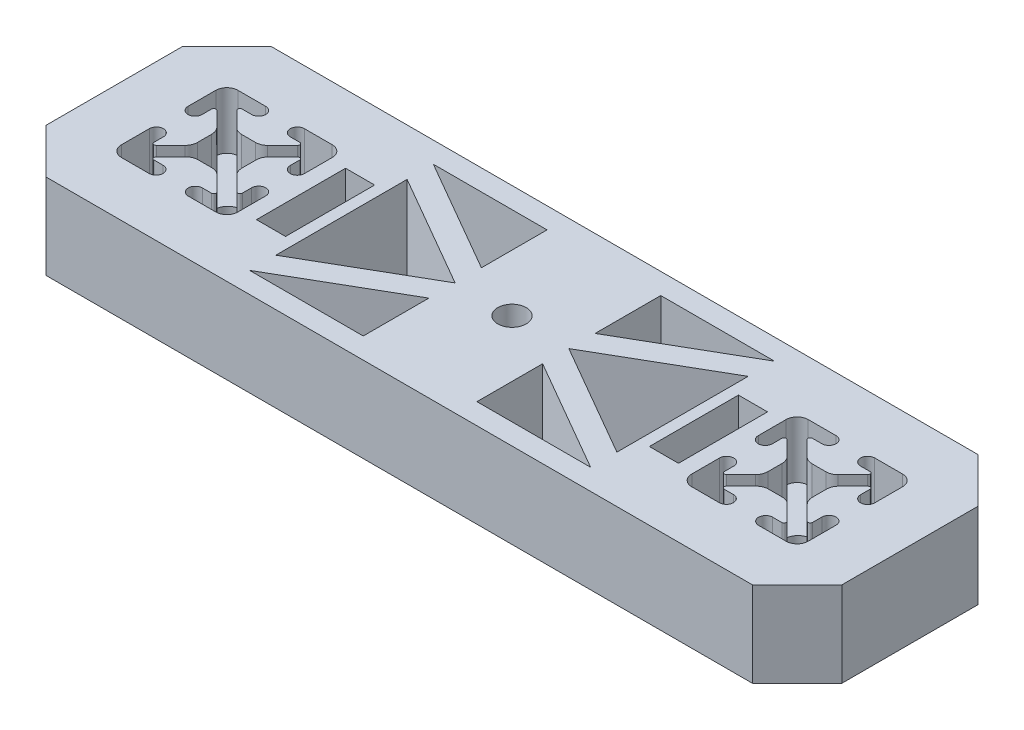
SolidWorks part; units mm, degrees
ref_plane "Front" through (0, 0, 0) normal (0, 0, 1) x (1, 0, 0)
ref_plane "Top" through (0, 0, 0) normal (0, 1, 0) x (1, 0, 0)
ref_plane "Right" through (0, 0, 0) normal (1, 0, 0) x (0, 0, -1)
sketch "Sketch1" plane through (0, 0, 0) normal (0, 1, 0) x (1, 0, 0)
  line L1 (0, 0) -> (177.8, 0)
  line L2 (0, 0) -> (0, 50.4)
  line L3 (0, 50.4) -> (177.8, 50.4)
  line L4 (177.8, 0) -> (177.8, 50.4)
  dimension "D1" = 177.8
  dimension "D2" = 50.4
extrude "Boss-Extrude1" add sketch "Sketch1" along normal blind 6.35
sketch "Sketch2" plane through (0, 6.35, 0) normal (0, 1, 0) x (1, 0, 0)
  line L0 (37.6996, 29.52) -> (37.6996, 35.7372) construction
  line L1 (35.7368, 37.7) -> (29.5196, 37.7) construction
  line L2 (29.5196, 35.56) -> (31.619, 35.56) construction
  line L3 (32.3326, 33.8353) -> (28.9966, 30.504) construction
  line L4 (26.7566, 29.5771) -> (23.643, 29.5771) construction
  line L5 (21.403, 30.504) -> (18.067, 33.8353) construction
  line L6 (18.7806, 35.56) -> (20.88, 35.56) construction
  line L7 (20.88, 37.7) -> (14.6628, 37.7) construction
  line L8 (12.7, 35.7372) -> (12.7, 29.52) construction
  line L9 (14.84, 29.52) -> (14.84, 31.5965) construction
  line L10 (16.5637, 32.3112) -> (19.7659, 29.1135) construction
  line L11 (20.743, 26.7568) -> (20.743, 23.6432) construction
  line L12 (19.7659, 21.2865) -> (16.5637, 18.0888) construction
  line L13 (14.84, 18.8035) -> (14.84, 20.88) construction
  line L14 (12.7, 20.88) -> (12.7, 14.6628) construction
  line L15 (14.6628, 12.7) -> (20.8121, 12.7) construction
  line L16 (20.8121, 14.84) -> (18.7806, 14.84) construction
  line L17 (18.067, 16.5647) -> (21.403, 19.896) construction
  line L18 (23.643, 20.8229) -> (26.7566, 20.8229) construction
  line L19 (28.9966, 19.896) -> (32.3326, 16.5647) construction
  line L20 (31.619, 14.84) -> (29.5875, 14.84) construction
  line L21 (29.5875, 12.7) -> (35.7368, 12.7) construction
  line L22 (37.6996, 14.6628) -> (37.6996, 20.88) construction
  line L23 (35.5596, 20.88) -> (35.5596, 18.8035) construction
  line L24 (33.8359, 18.0888) -> (30.6337, 21.2865) construction
  line L25 (29.6566, 23.6432) -> (29.6566, 26.7568) construction
  line L26 (30.6337, 29.1135) -> (33.8359, 32.3112) construction
  line L27 (35.5596, 31.5965) -> (35.5596, 29.52) construction
  line L28 (0, 50.4) -> (0, 0) construction
  line L29 (177.8, 50.4) -> (0, 50.4) construction
  line L30 (0, 0) -> (177.8, 0) construction
  line L31 (88.9, 50.4) -> (88.9, 0) construction
  line L32 (142.2404, 31.5965) -> (142.2404, 29.52) construction
  line L33 (147.1663, 29.1135) -> (143.9641, 32.3112) construction
  line L34 (148.1434, 23.6432) -> (148.1434, 26.7568) construction
  line L35 (143.9641, 18.0888) -> (147.1663, 21.2865) construction
  line L36 (142.2404, 20.88) -> (142.2404, 18.8035) construction
  line L37 (140.1004, 14.6628) -> (140.1004, 20.88) construction
  line L38 (148.2125, 12.7) -> (142.0632, 12.7) construction
  line L39 (146.181, 14.84) -> (148.2125, 14.84) construction
  line L40 (148.8034, 19.896) -> (145.4674, 16.5647) construction
  line L41 (154.157, 20.8229) -> (151.0434, 20.8229) construction
  line L42 (159.733, 16.5647) -> (156.397, 19.896) construction
  line L43 (156.9879, 14.84) -> (159.0194, 14.84) construction
  line L44 (163.1372, 12.7) -> (156.9879, 12.7) construction
  line L45 (165.1, 20.88) -> (165.1, 14.6628) construction
  line L46 (162.96, 18.8035) -> (162.96, 20.88) construction
  line L47 (158.0341, 21.2865) -> (161.2363, 18.0888) construction
  line L48 (157.057, 26.7568) -> (157.057, 23.6432) construction
  line L49 (161.2363, 32.3112) -> (158.0341, 29.1135) construction
  line L50 (162.96, 29.52) -> (162.96, 31.5965) construction
  line L51 (165.1, 35.7372) -> (165.1, 29.52) construction
  line L52 (156.92, 37.7) -> (163.1372, 37.7) construction
  line L53 (159.0194, 35.56) -> (156.92, 35.56) construction
  line L54 (156.397, 30.504) -> (159.733, 33.8353) construction
  line L55 (151.0434, 29.5771) -> (154.157, 29.5771) construction
  line L56 (145.4674, 33.8353) -> (148.8034, 30.504) construction
  line L57 (148.2804, 35.56) -> (146.181, 35.56) construction
  line L58 (142.0632, 37.7) -> (148.2804, 37.7) construction
  line L59 (140.1004, 29.52) -> (140.1004, 35.7372) construction
  line L60 (38.2076, 29.52) -> (38.2076, 35.7372)
  line L62 (0, 50.4) -> (0, 0)
  line L63 (0, 0) -> (177.8, 0)
  line L64 (177.8, 50.4) -> (177.8, 0)
  line L65 (35.7368, 38.208) -> (29.5196, 38.208)
  line L66 (29.5196, 35.052) -> (31.619, 35.052)
  line L67 (31.9737, 34.1948) -> (28.6376, 30.8635)
  line L68 (26.7566, 30.0851) -> (23.643, 30.0851)
  line L69 (21.762, 30.8635) -> (18.4259, 34.1948)
  line L70 (18.7806, 35.052) -> (20.88, 35.052)
  line L71 (20.88, 38.208) -> (14.6628, 38.208)
  line L72 (12.192, 35.7372) -> (12.192, 29.52)
  line L73 (15.348, 29.52) -> (15.348, 31.5965)
  line L74 (16.2047, 31.9517) -> (19.4069, 28.7541)
  line L75 (20.235, 26.7568) -> (20.235, 23.6432)
  line L76 (19.4069, 21.6459) -> (16.2047, 18.4483)
  line L77 (15.348, 18.8035) -> (15.348, 20.88)
  line L78 (12.192, 20.88) -> (12.192, 14.6628)
  line L79 (14.6628, 12.192) -> (20.8121, 12.192)
  line L80 (20.8121, 15.348) -> (18.7806, 15.348)
  line L81 (18.4259, 16.2052) -> (21.762, 19.5365)
  line L82 (23.643, 20.3149) -> (26.7566, 20.3149)
  line L83 (28.6376, 19.5365) -> (31.9737, 16.2052)
  line L84 (31.619, 15.348) -> (29.5875, 15.348)
  line L85 (29.5875, 12.192) -> (35.7368, 12.192)
  line L86 (38.2076, 14.6628) -> (38.2076, 20.88)
  line L87 (35.0516, 20.88) -> (35.0516, 18.8035)
  line L88 (34.1949, 18.4483) -> (30.9927, 21.6459)
  line L89 (30.1646, 23.6432) -> (30.1646, 26.7568)
  line L90 (30.9927, 28.7541) -> (34.1949, 31.9517)
  line L91 (35.0516, 31.5965) -> (35.0516, 29.52)
  line L92 (142.7484, 31.5965) -> (142.7484, 29.52)
  line L93 (139.5924, 29.52) -> (139.5924, 35.7372)
  line L94 (142.0632, 38.208) -> (148.2804, 38.208)
  line L95 (148.2804, 35.052) -> (146.181, 35.052)
  line L96 (145.8263, 34.1948) -> (149.1624, 30.8635)
  line L97 (151.0434, 30.0851) -> (154.157, 30.0851)
  line L98 (156.038, 30.8635) -> (159.3741, 34.1948)
  line L99 (159.0194, 35.052) -> (156.92, 35.052)
  line L100 (156.92, 38.208) -> (163.1372, 38.208)
  line L101 (165.608, 35.7372) -> (165.608, 29.52)
  line L102 (162.452, 29.52) -> (162.452, 31.5965)
  line L103 (161.5953, 31.9517) -> (158.3931, 28.7541)
  line L104 (157.565, 26.7568) -> (157.565, 23.6432)
  line L105 (158.3931, 21.6459) -> (161.5953, 18.4483)
  line L106 (162.452, 18.8035) -> (162.452, 20.88)
  line L107 (165.608, 20.88) -> (165.608, 14.6628)
  line L108 (163.1372, 12.192) -> (156.9879, 12.192)
  line L109 (156.9879, 15.348) -> (159.0194, 15.348)
  line L110 (159.3741, 16.2052) -> (156.038, 19.5365)
  line L111 (154.157, 20.3149) -> (151.0434, 20.3149)
  line L112 (149.1624, 19.5365) -> (145.8263, 16.2052)
  line L113 (146.181, 15.348) -> (148.2125, 15.348)
  line L114 (148.2125, 12.192) -> (142.0632, 12.192)
  line L115 (139.5924, 14.6628) -> (139.5924, 20.88)
  line L116 (142.7484, 20.88) -> (142.7484, 18.8035)
  line L117 (143.6051, 18.4483) -> (146.8073, 21.6459)
  line L118 (147.6354, 23.6432) -> (147.6354, 26.7568)
  line L119 (146.8073, 28.7541) -> (143.6051, 31.9517)
  line L120 (177.8, 50.4) -> (0, 50.4)
  arc A1 (37.6996, 35.7372) -> (35.7368, 37.7) centre (35.7368, 35.7372) ccw construction
  arc A2 (29.5196, 37.7) -> (29.5196, 35.56) centre (29.5196, 36.63) ccw construction
  arc A3 (31.619, 35.56) -> (32.3326, 33.8353) centre (31.619, 34.55) cw construction
  arc A4 (28.9966, 30.504) -> (26.7566, 29.5771) centre (26.7566, 32.7471) cw construction
  arc A5 (23.643, 29.5771) -> (21.403, 30.504) centre (23.643, 32.7471) cw construction
  arc A6 (18.067, 33.8353) -> (18.7806, 35.56) centre (18.7806, 34.55) cw construction
  arc A7 (20.88, 35.56) -> (20.88, 37.7) centre (20.88, 36.63) ccw construction
  arc A8 (14.6628, 37.7) -> (12.7, 35.7372) centre (14.6628, 35.7372) ccw construction
  arc A9 (12.7, 29.52) -> (14.84, 29.52) centre (13.77, 29.52) ccw construction
  arc A10 (14.84, 31.5965) -> (16.5637, 32.3112) centre (15.85, 31.5965) cw construction
  arc A11 (19.7659, 29.1135) -> (20.743, 26.7568) centre (17.4126, 26.7568) cw construction
  arc A12 (20.743, 23.6432) -> (19.7659, 21.2865) centre (17.4126, 23.6432) cw construction
  arc A13 (16.5637, 18.0888) -> (14.84, 18.8035) centre (15.85, 18.8035) cw construction
  arc A14 (14.84, 20.88) -> (12.7, 20.88) centre (13.77, 20.88) ccw construction
  arc A15 (12.7, 14.6628) -> (14.6628, 12.7) centre (14.6628, 14.6628) ccw construction
  arc A16 (20.8121, 12.7) -> (20.8121, 14.84) centre (20.8121, 13.77) ccw construction
  arc A17 (18.7806, 14.84) -> (18.067, 16.5647) centre (18.7806, 15.85) cw construction
  arc A18 (21.403, 19.896) -> (23.643, 20.8229) centre (23.643, 17.6529) cw construction
  arc A19 (26.7566, 20.8229) -> (28.9966, 19.896) centre (26.7566, 17.6529) cw construction
  arc A20 (32.3326, 16.5647) -> (31.619, 14.84) centre (31.619, 15.85) cw construction
  arc A21 (29.5875, 14.84) -> (29.5875, 12.7) centre (29.5875, 13.77) ccw construction
  arc A22 (35.7368, 12.7) -> (37.6996, 14.6628) centre (35.7368, 14.6628) ccw construction
  arc A23 (37.6996, 20.88) -> (35.5596, 20.88) centre (36.6296, 20.88) ccw construction
  arc A24 (35.5596, 18.8035) -> (33.8359, 18.0888) centre (34.5496, 18.8035) cw construction
  arc A25 (30.6337, 21.2865) -> (29.6566, 23.6432) centre (32.987, 23.6432) cw construction
  arc A26 (29.6566, 26.7568) -> (30.6337, 29.1135) centre (32.987, 26.7568) cw construction
  arc A27 (33.8359, 32.3112) -> (35.5596, 31.5965) centre (34.5496, 31.5965) cw construction
  arc A28 (35.5596, 29.52) -> (37.6996, 29.52) centre (36.6296, 29.52) ccw construction
  arc A29 (142.2404, 29.52) -> (140.1004, 29.52) centre (141.1704, 29.52) cw construction
  arc A30 (143.9641, 32.3112) -> (142.2404, 31.5965) centre (143.2504, 31.5965) ccw construction
  arc A31 (148.1434, 26.7568) -> (147.1663, 29.1135) centre (144.813, 26.7568) ccw construction
  arc A32 (147.1663, 21.2865) -> (148.1434, 23.6432) centre (144.813, 23.6432) ccw construction
  arc A33 (142.2404, 18.8035) -> (143.9641, 18.0888) centre (143.2504, 18.8035) ccw construction
  arc A34 (140.1004, 20.88) -> (142.2404, 20.88) centre (141.1704, 20.88) cw construction
  arc A35 (142.0632, 12.7) -> (140.1004, 14.6628) centre (142.0632, 14.6628) cw construction
  arc A36 (148.2125, 14.84) -> (148.2125, 12.7) centre (148.2125, 13.77) cw construction
  arc A37 (145.4674, 16.5647) -> (146.181, 14.84) centre (146.181, 15.85) ccw construction
  arc A38 (151.0434, 20.8229) -> (148.8034, 19.896) centre (151.0434, 17.6529) ccw construction
  arc A39 (156.397, 19.896) -> (154.157, 20.8229) centre (154.157, 17.6529) ccw construction
  arc A40 (159.0194, 14.84) -> (159.733, 16.5647) centre (159.0194, 15.85) ccw construction
  arc A41 (156.9879, 12.7) -> (156.9879, 14.84) centre (156.9879, 13.77) cw construction
  arc A42 (165.1, 14.6628) -> (163.1372, 12.7) centre (163.1372, 14.6628) cw construction
  arc A43 (162.96, 20.88) -> (165.1, 20.88) centre (164.03, 20.88) cw construction
  arc A44 (161.2363, 18.0888) -> (162.96, 18.8035) centre (161.95, 18.8035) ccw construction
  arc A45 (157.057, 23.6432) -> (158.0341, 21.2865) centre (160.3874, 23.6432) ccw construction
  arc A46 (158.0341, 29.1135) -> (157.057, 26.7568) centre (160.3874, 26.7568) ccw construction
  arc A47 (162.96, 31.5965) -> (161.2363, 32.3112) centre (161.95, 31.5965) ccw construction
  arc A48 (165.1, 29.52) -> (162.96, 29.52) centre (164.03, 29.52) cw construction
  arc A49 (163.1372, 37.7) -> (165.1, 35.7372) centre (163.1372, 35.7372) cw construction
  arc A50 (156.92, 35.56) -> (156.92, 37.7) centre (156.92, 36.63) cw construction
  arc A51 (159.733, 33.8353) -> (159.0194, 35.56) centre (159.0194, 34.55) ccw construction
  arc A52 (154.157, 29.5771) -> (156.397, 30.504) centre (154.157, 32.7471) ccw construction
  arc A53 (148.8034, 30.504) -> (151.0434, 29.5771) centre (151.0434, 32.7471) ccw construction
  arc A54 (146.181, 35.56) -> (145.4674, 33.8353) centre (146.181, 34.55) ccw construction
  arc A55 (148.2804, 37.7) -> (148.2804, 35.56) centre (148.2804, 36.63) cw construction
  arc A56 (140.1004, 35.7372) -> (142.0632, 37.7) centre (142.0632, 35.7372) cw construction
  arc A58 (38.2076, 35.7372) -> (35.7368, 38.208) centre (35.7368, 35.7372) ccw
  arc A59 (29.5196, 38.208) -> (29.5196, 35.052) centre (29.5196, 36.63) ccw
  arc A60 (31.619, 35.052) -> (31.9737, 34.1948) centre (31.619, 34.55) cw
  arc A61 (28.6376, 30.8635) -> (26.7566, 30.0851) centre (26.7566, 32.7471) cw
  arc A62 (23.643, 30.0851) -> (21.762, 30.8635) centre (23.643, 32.7471) cw
  arc A63 (18.4259, 34.1948) -> (18.7806, 35.052) centre (18.7806, 34.55) cw
  arc A64 (20.88, 35.052) -> (20.88, 38.208) centre (20.88, 36.63) ccw
  arc A65 (14.6628, 38.208) -> (12.192, 35.7372) centre (14.6628, 35.7372) ccw
  arc A66 (12.192, 29.52) -> (15.348, 29.52) centre (13.77, 29.52) ccw
  arc A67 (15.348, 31.5965) -> (16.2047, 31.9517) centre (15.85, 31.5965) cw
  arc A68 (19.4069, 28.7541) -> (20.235, 26.7568) centre (17.4126, 26.7568) cw
  arc A69 (20.235, 23.6432) -> (19.4069, 21.6459) centre (17.4126, 23.6432) cw
  arc A70 (16.2047, 18.4483) -> (15.348, 18.8035) centre (15.85, 18.8035) cw
  arc A71 (15.348, 20.88) -> (12.192, 20.88) centre (13.77, 20.88) ccw
  arc A72 (12.192, 14.6628) -> (14.6628, 12.192) centre (14.6628, 14.6628) ccw
  arc A73 (20.8121, 12.192) -> (20.8121, 15.348) centre (20.8121, 13.77) ccw
  arc A74 (18.7806, 15.348) -> (18.4259, 16.2052) centre (18.7806, 15.85) cw
  arc A75 (21.762, 19.5365) -> (23.643, 20.3149) centre (23.643, 17.6529) cw
  arc A76 (26.7566, 20.3149) -> (28.6376, 19.5365) centre (26.7566, 17.6529) cw
  arc A77 (31.9737, 16.2052) -> (31.619, 15.348) centre (31.619, 15.85) cw
  arc A78 (29.5875, 15.348) -> (29.5875, 12.192) centre (29.5875, 13.77) ccw
  arc A79 (35.7368, 12.192) -> (38.2076, 14.6628) centre (35.7368, 14.6628) ccw
  arc A80 (38.2076, 20.88) -> (35.0516, 20.88) centre (36.6296, 20.88) ccw
  arc A81 (35.0516, 18.8035) -> (34.1949, 18.4483) centre (34.5496, 18.8035) cw
  arc A82 (30.9927, 21.6459) -> (30.1646, 23.6432) centre (32.987, 23.6432) cw
  arc A83 (30.1646, 26.7568) -> (30.9927, 28.7541) centre (32.987, 26.7568) cw
  arc A84 (34.1949, 31.9517) -> (35.0516, 31.5965) centre (34.5496, 31.5965) cw
  arc A85 (35.0516, 29.52) -> (38.2076, 29.52) centre (36.6296, 29.52) ccw
  arc A86 (142.7484, 29.52) -> (139.5924, 29.52) centre (141.1704, 29.52) cw
  arc A87 (139.5924, 35.7372) -> (142.0632, 38.208) centre (142.0632, 35.7372) cw
  arc A88 (148.2804, 38.208) -> (148.2804, 35.052) centre (148.2804, 36.63) cw
  arc A89 (146.181, 35.052) -> (145.8263, 34.1948) centre (146.181, 34.55) ccw
  arc A90 (149.1624, 30.8635) -> (151.0434, 30.0851) centre (151.0434, 32.7471) ccw
  arc A91 (154.157, 30.0851) -> (156.038, 30.8635) centre (154.157, 32.7471) ccw
  arc A92 (159.3741, 34.1948) -> (159.0194, 35.052) centre (159.0194, 34.55) ccw
  arc A93 (156.92, 35.052) -> (156.92, 38.208) centre (156.92, 36.63) cw
  arc A94 (163.1372, 38.208) -> (165.608, 35.7372) centre (163.1372, 35.7372) cw
  arc A95 (165.608, 29.52) -> (162.452, 29.52) centre (164.03, 29.52) cw
  arc A96 (162.452, 31.5965) -> (161.5953, 31.9517) centre (161.95, 31.5965) ccw
  arc A97 (158.3931, 28.7541) -> (157.565, 26.7568) centre (160.3874, 26.7568) ccw
  arc A98 (157.565, 23.6432) -> (158.3931, 21.6459) centre (160.3874, 23.6432) ccw
  arc A99 (161.5953, 18.4483) -> (162.452, 18.8035) centre (161.95, 18.8035) ccw
  arc A100 (162.452, 20.88) -> (165.608, 20.88) centre (164.03, 20.88) cw
  arc A101 (165.608, 14.6628) -> (163.1372, 12.192) centre (163.1372, 14.6628) cw
  arc A102 (156.9879, 12.192) -> (156.9879, 15.348) centre (156.9879, 13.77) cw
  arc A103 (159.0194, 15.348) -> (159.3741, 16.2052) centre (159.0194, 15.85) ccw
  arc A104 (156.038, 19.5365) -> (154.157, 20.3149) centre (154.157, 17.6529) ccw
  arc A105 (151.0434, 20.3149) -> (149.1624, 19.5365) centre (151.0434, 17.6529) ccw
  arc A106 (145.8263, 16.2052) -> (146.181, 15.348) centre (146.181, 15.85) ccw
  arc A107 (148.2125, 15.348) -> (148.2125, 12.192) centre (148.2125, 13.77) cw
  arc A108 (142.0632, 12.192) -> (139.5924, 14.6628) centre (142.0632, 14.6628) cw
  arc A109 (139.5924, 20.88) -> (142.7484, 20.88) centre (141.1704, 20.88) cw
  arc A110 (142.7484, 18.8035) -> (143.6051, 18.4483) centre (143.2504, 18.8035) ccw
  arc A111 (146.8073, 21.6459) -> (147.6354, 23.6432) centre (144.813, 23.6432) ccw
  arc A112 (147.6354, 26.7568) -> (146.8073, 28.7541) centre (144.813, 26.7568) ccw
  arc A113 (143.6051, 31.9517) -> (142.7484, 31.5965) centre (143.2504, 31.5965) ccw
  dimension "D2" = 1.07
  dimension "D3" = 3.17
  dimension "D4" = 3.3305
  dimension "D8" = 1.9628
  dimension "D9" = 1.01
  dimension "D5" = 12.7
  dimension "D6" = 12.7
  dimension "D7" = 12.7
  dimension "D10" = 16.5637
  dimension "D12" = 0.508
  dimension "D13" = 0.508
extrude "Boss-Extrude2" add sketch "Sketch2" along normal blind 12.7
sketch "Sketch3" plane through (0, 19.05, 0) normal (0, 1, 0) x (1, 0, 0)
  line L0 (177.8, 50.4) -> (0, 50.4) construction
  line L1 (0, 50.4) -> (0, 0) construction
  circle A0 centre (88.9, 25.2) radius 3.175
  point P4 (88.9, 50.4)
  point P7 (0, 25.2)
  dimension "D1" = 6.35
extrude "Cut-Extrude1" cut sketch "Sketch3" against normal through all
sketch "Sketch4" plane through (0, 19.05, 0) normal (0, 1, 0) x (1, 0, 0)
  line L0 (50.8, 45.7306) -> (76.2, 45.7306)
  line L1 (76.2, 45.7306) -> (76.2, 31.0659)
  line L2 (76.2, 31.0659) -> (50.8, 45.7306)
  line L3 (76.2, 19.3341) -> (76.2, 4.6694)
  line L4 (76.2, 4.6694) -> (50.8, 4.6694)
  line L5 (50.8, 4.6694) -> (76.2, 19.3341)
  line L6 (50.8, 39.8647) -> (50.8, 10.5353)
  line L7 (50.8, 10.5353) -> (76.2, 25.2)
  line L8 (76.2, 25.2) -> (50.8, 39.8647)
  line L9 (0, 50.4) -> (0, 0) construction
  line L10 (88.9, 50.4) -> (88.9, 0) construction
  line L11 (177.8, 50.4) -> (0, 50.4) construction
  line L12 (0, 0) -> (177.8, 0) construction
  line L13 (101.6, 25.2) -> (127, 39.8647)
  line L14 (127, 10.5353) -> (101.6, 25.2)
  line L15 (127, 39.8647) -> (127, 10.5353)
  line L16 (127, 4.6694) -> (101.6, 19.3341)
  line L17 (101.6, 4.6694) -> (127, 4.6694)
  line L18 (101.6, 19.3341) -> (101.6, 4.6694)
  line L19 (101.6, 31.0659) -> (127, 45.7306)
  line L20 (101.6, 45.7306) -> (101.6, 31.0659)
  line L21 (127, 45.7306) -> (101.6, 45.7306)
  point P18 (88.9, 25.2)
  dimension "D1" = 25.4
  dimension "D2" = 25.4
  dimension "D3" = 50.8
  dimension "D4" = 5.08
  dimension "D5" = 5.08
  dimension "D7" = 60
extrude "Cut-Extrude2" cut sketch "Sketch4" against normal through all
chamfer "Chamfer1" distance 10 angle 45 4 edges at (177.8, 9.525, -50.4) (177.8, 9.525, 0) (0, 9.525, 0) (0, 9.525, -50.4)
sketch "Sketch5" plane through (0, 19.05, 0) normal (0, 1, 0) x (1, 0, 0)
  line L0 (0, 40.4) -> (0, 10) construction
  line L1 (41.7636, 35.15) -> (48.2636, 35.15)
  line L2 (41.7636, 35.15) -> (41.7636, 15.25)
  line L3 (41.7636, 15.25) -> (48.2636, 15.25)
  line L4 (48.2636, 35.15) -> (48.2636, 15.25)
  line L5 (38.2076, 29.52) -> (38.2076, 35.7372) construction
  point P6 (0, 25.2)
  point P7 (48.2636, 25.2)
  dimension "D1" = 6.5
  dimension "D2" = 19.9
  dimension "D3" = 3.556
extrude "Cut-Extrude3" cut sketch "Sketch5" against normal blind 10.2
sketch "Sketch6" plane through (0, 8.85, 0) normal (0, 1, 0) x (1, 0, 0)
  line L0 (48.2636, 15.25) -> (48.2636, 35.15) construction
  line L1 (41.7636, 35.15) -> (48.2636, 35.15)
  line L2 (41.7636, 35.15) -> (41.7636, 30.578)
  line L3 (41.7636, 30.578) -> (48.2636, 30.578)
  line L4 (48.2636, 35.15) -> (48.2636, 30.578)
  line L5 (41.7636, 35.15) -> (41.7636, 15.25) construction
  line L6 (48.2636, 15.25) -> (48.2636, 35.15) construction
  line L7 (41.7636, 27.486) -> (48.2636, 27.486)
  line L8 (41.7636, 27.486) -> (41.7636, 22.914)
  line L9 (41.7636, 22.914) -> (48.2636, 22.914)
  line L10 (48.2636, 27.486) -> (48.2636, 22.914)
  line L12 (41.7636, 15.25) -> (48.2636, 15.25)
  line L13 (41.7636, 15.25) -> (41.7636, 19.822)
  line L14 (41.7636, 19.822) -> (48.2636, 19.822)
  line L15 (48.2636, 15.25) -> (48.2636, 19.822)
  line L16 (41.7636, 25.2) -> (0, 25.2) construction
  line L17 (0, 40.4) -> (0, 10) construction
  dimension "D1" = 4.572
extrude "Cut-Extrude4" cut sketch "Sketch6" against normal through all
ref_plane "Plane1" through (88.9, 0, 0) normal (-1, 0, 0) x (0, 0, 1)
mirror "Mirror1" about plane through (88.9, 0, 0) normal (-1, 0, 0) of "Cut-Extrude4", "Cut-Extrude3"
sketch "Sketch7" plane through (0, 19.05, 0) normal (0, 1, 0) x (1, 0, 0)
  line L0 (26.7566, 30.0851) -> (23.643, 30.0851) construction
  line L1 (30.1646, 23.6432) -> (30.1646, 26.7568) construction
  circle A0 centre (25.3386, 25.2591) radius 2.921
  dimension "D3" = 5.842
  dimension "D1" = 4.826
  dimension "D2" = 4.826
extrude "Cut-Extrude5" cut sketch "Sketch7" against normal through all both and the other way through all
sketch "Sketch8" plane through (0, 6.35, 0) normal (0, 1, 0) x (1, 0, 0)
  line L0 (154.157, 30.0851) -> (151.0434, 30.0851) construction
  line L1 (157.565, 23.6432) -> (157.565, 26.7568) construction
  circle A0 centre (152.739, 25.2591) radius 2.921
  dimension "D3" = 5.842
  dimension "D1" = 4.826
  dimension "D2" = 4.826
extrude "Cut-Extrude6" cut sketch "Sketch8" against normal through all both and the other way through all
